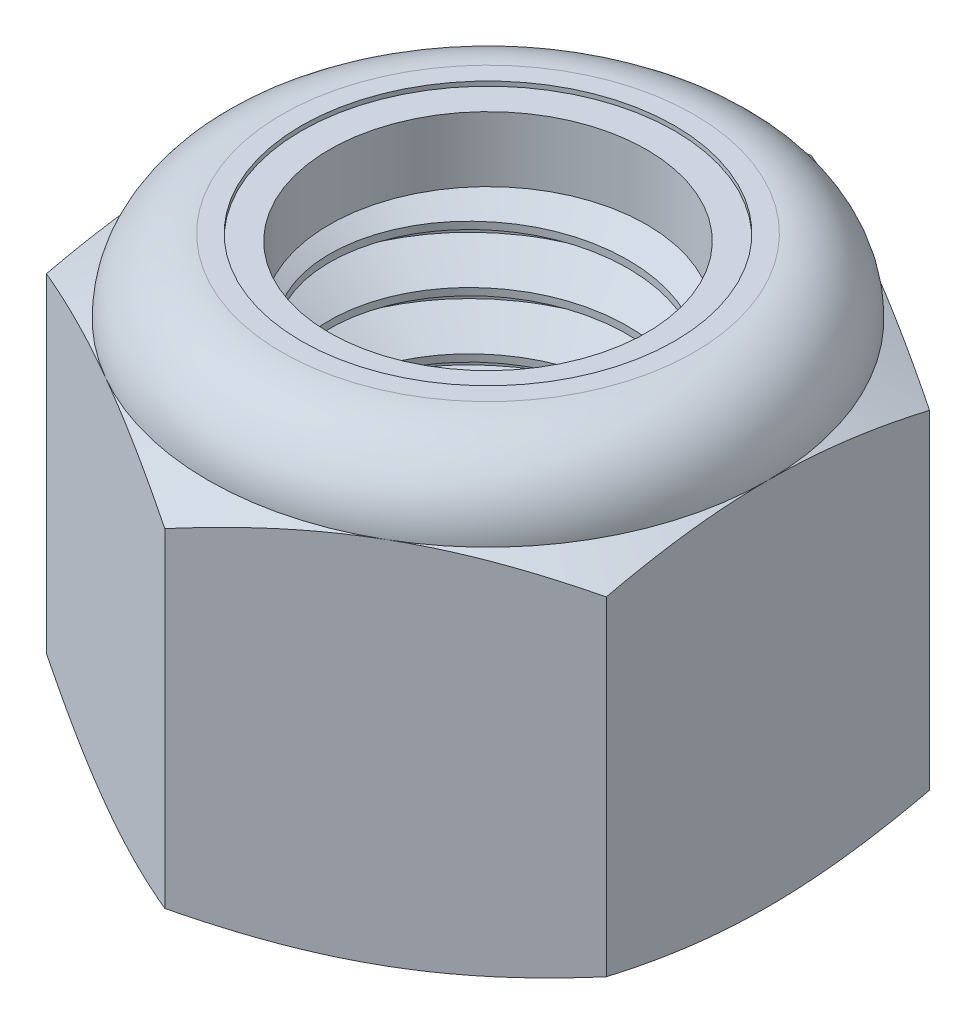
SolidWorks part; units mm, degrees
note: '?' marks a value the reader was unsure of.
ref_plane "Front" through (0, 0, 0) normal (0, 0, 1) x (1, 0, 0)
ref_plane "Top" through (0, 0, 0) normal (0, 1, 0) x (1, 0, 0)
ref_plane "Right" through (0, 0, 0) normal (1, 0, 0) x (0, 0, -1)
sketch "Sketch8" plane through (0, 0, 0) normal (1, 0, 0) x (0, 0, -1)
  line L0 (0, 0) -> (0, 15.0812) construction
  line L1 (9.525, 0) -> (-9.525, 0) construction
  line L2 (-6.35, 15.0812) -> (6.35, 15.0812) construction
  line L3 (6.35, 15.0812) -> (6.35, 13.1274) construction
sketch "Sketch1" plane through (0, 0, 0) normal (0, 1, 0) x (1, 0, 0)
  line L1 (0, 10.9985) -> (-9.525, 5.4993)
  line L2 (-9.525, 5.4993) -> (-9.525, -5.4993)
  line L3 (-9.525, -5.4993) -> (0, -10.9985)
  line L4 (0, -10.9985) -> (9.525, -5.4993)
  line L5 (9.525, -5.4993) -> (9.525, 5.4993)
  line L6 (9.525, 5.4993) -> (0, 10.9985)
  circle A0 centre (0, 0) radius 9.525 construction
  circle A1 centre (0, 0) radius 6.35
extrude "Extrude1" add sketch "Sketch1" along normal up to vertex (15.0813 mm away) up to point (0, 15.0812, 0)
sketch "Sketch5" plane through (0, 0, 0) normal (1, 0, 0) x (0, 0, -1)
  line L0 (0, 0) -> (9.525, 0)
  line L1 (9.525, 0) -> (10.9985, 0.6871)
  line L2 (10.9985, 0.6871) -> (10.9985, 11.8806)
  line L3 (10.9985, 11.8806) -> (9.525, 12.5677)
  line L4 (7.0115, 15.0812) -> (7.0115, 16.3512)
  line L5 (7.0115, 16.3512) -> (12.2685, 16.3512)
  line L6 (12.2685, 16.3512) -> (12.2685, -1.27)
  line L7 (12.2685, -1.27) -> (0, -1.27)
  line L8 (0, -1.27) -> (0, 0)
  line L9 (9.525, 12.5677) -> (9.525, 0) construction
  line L12 (10.9985, 15.0812) -> (10.9985, 0) construction
  line L13 (10.9985, 7.5406) -> (12.2685, 7.5406) construction
  line L15 (0, 0) -> (0, 16.3512) construction
  line L18 (9.525, 0) -> (-9.525, 0) construction
  line L19 (5.4993, 15.0812) -> (10.9985, 15.0812) construction
  line L20 (0, 16.3512) -> (7.0115, 16.3512) construction
  line L21 (5.4993, 0) -> (10.9985, 0) construction
  arc A0 (9.525, 12.5677) -> (7.0115, 15.0812) centre (7.0115, 12.5677) ccw
  dimension "D1" = 25
  dimension "D2" = 1.27
  dimension "D4" = 2.5135
revolve "Cut-Revolve3" cut sketch "Sketch5" angle 360 about L15
sketch "Sketch4" plane through (0, 0, 0) normal (1, 0, 0) x (0, 0, -1)
  line L0 (0, 12.5677) -> (6.985, 12.5677)
  line L1 (6.985, 12.5677) -> (0, 9.3105)
  line L3 (0, 3.2572) -> (6.985, 0)
  line L4 (6.985, 0) -> (0, 0)
  line L5 (0, 0) -> (0, 12.5677) construction
  line L10 (0, 0) -> (0, 15.0812) construction
  line L11 (0, 3.2572) -> (0, 0)
  line L12 (0, 12.5677) -> (0, 9.3105)
  line L13 (8.2489, 12.5677) -> (0, 12.5677) construction
  dimension "D1" = 25
  dimension "D2" = 13.97
sketch "Sketch6" plane through (0, 0, 0) normal (1, 0, 0) x (0, 0, -1)
  line L0 (0, 12.5677) -> (9.3726, 12.5677)
  line L1 (7.0115, 14.9288) -> (3.5057, 14.9288)
  line L2 (0, 16.3512) -> (0, 12.5677)
  line L3 (3.5057, 16.3512) -> (0, 16.3512)
  line L4 (0, 16.3512) -> (7.0115, 16.3512) construction
  line L5 (0, 0) -> (0, 16.3512) construction
  line L6 (0, 16.3512) -> (0, 0) construction
  line L7 (3.5057, 14.9288) -> (3.5057, 16.3512)
  line L8 (7.0115, 15.0812) -> (7.0115, 14.9288) construction
  line L9 (3.5057, 14.9288) -> (0, 14.9288) construction
  line L10 (0, 14.9288) -> (0, 9.3105) construction
  arc A0 (9.3726, 12.5677) -> (7.0115, 14.9288) centre (7.0115, 12.5677) ccw
  arc A1 (9.525, 12.5677) -> (7.0115, 15.0812) centre (7.0115, 12.5677) ccw construction
  dimension "D1" = 0.1524
revolve "Cut-Revolve4" cut sketch "Sketch6" angle 360 about L6
revolve "Cut-Revolve2" cut sketch "Sketch4" angle 360 about L5
sketch "Sketch7" plane through (0, 0, 0) normal (1, 0, 0) x (0, 0, -1)
  line L0 (5.3975, 12.6439) -> (9.2951, 12.6439)
  line L1 (7.0115, 14.8526) -> (5.3975, 14.8526)
  line L2 (5.3975, 14.8526) -> (5.3975, 12.6439)
  line L3 (5.3975, 12.6439) -> (0, 12.6439) construction
  line L4 (0, 12.6439) -> (0, 14.8526) construction
  line L5 (0, 14.8526) -> (5.3975, 14.8526) construction
  line L6 (5.3975, 12.6439) -> (5.3975, 12.5677) construction
  line L7 (0, 12.5677) -> (9.3726, 12.5677) construction
  line L8 (7.0115, 14.8526) -> (7.0115, 14.9288) construction
  arc A0 (9.2951, 12.6439) -> (7.0115, 14.8526) centre (7.0115, 12.5677) ccw
  arc A2 (9.3726, 12.5677) -> (7.0115, 14.9288) centre (7.0115, 12.5677) ccw construction
  dimension "D1" = 0.0762
  dimension "D2" = 10.795
revolve "Revolve2" add sketch "Sketch7" angle 360 about L4
sketch "Sketch2" plane through (0, 0, 0) normal (1, 0, 0) x (0, 0, -1)
  line L0 (-6.35, 0) -> (-6.35, 12.5677) construction
  line L1 (0, 0) -> (6.35, 0)
  line L2 (0, 0) -> (0, 12.5677)
  line L3 (0, 12.5677) -> (6.35, 12.5677)
  line L4 (6.35, 0) -> (6.35, 12.5677)
  line L6 (8.2489, 12.5677) -> (9.525, 12.5677) construction
  line L7 (0, -6.35) -> (0, 0) construction
revolve "Revolve1" add sketch "Sketch2" angle 360 about L7
sketch "Sketch9" plane through (0, 0, 0) normal (1, 0, 0) x (0, 0, -1)
  line L0 (6.5615, 14.3994) -> (6.5615, 12.4456) construction
  line L1 (6.5615, 12.4456) -> (4.8694, 13.4225) construction
  line L2 (4.8694, 13.4225) -> (6.5615, 14.3994) construction
  line L3 (5.0809, 13.5446) -> (5.0809, 13.3004) construction
  line L4 (6.35, 14.2773) -> (6.35, 12.5677) construction
  line L5 (4.8694, 13.4225) -> (5.0809, 13.4225) construction
  line L6 (6.35, 13.4225) -> (6.5615, 13.4225) construction
  line L7 (6.4558, 13.4225) -> (6.4558, 14.3384) construction
  line L8 (6.5615, 12.4456) -> (6.4558, 14.3384)
  line L9 (6.4558, 14.3384) -> (5.0809, 13.5446)
  line L10 (5.0809, 13.5446) -> (5.0809, 13.3004)
  line L11 (5.0809, 13.3004) -> (6.5615, 12.4456)
  dimension "D1" = 1.9538
  dimension "D2" = 0.2442
sketch "Sketch10" plane through (0, 12.5677, 0) normal (0, 1, 0) x (1, 0, 0)
  circle A1 centre (0, 0) radius 6.35
  circle A2 centre (0, 0) radius 6.35
  dimension "D1" = 0
curve "Helix/Spiral1" pitch 1.9538 height 17.0351 turns 8.7187
sweep "Cut-Sweep1" cut profiles "Sketch9" path "Helix/Spiral1" align with end faces yes
sketch "Sketch11" plane through (0, 0, 0) normal (1, 0, 0) x (0, 0, -1)
  line L0 (0, 0) -> (0, 15.0812) construction
  line L1 (9.525, 0) -> (-9.525, 0) construction
  line L4 (0, 15.0812) -> (0, 0) construction
  line L5 (0, 7.5406) -> (6.35, 7.5406) construction
  line L6 (0, 0) -> (6.985, 0)
  line L7 (0, 3.2572) -> (0, 0)
  line L8 (6.985, 0) -> (0, 3.2572)
  dimension "D1" = 13.97
  dimension "D2" = 25
revolve "Revolve3" add sketch "Sketch11" angle 360 about L4
sketch "Sketch12" plane through (0, 0, 0) normal (1, 0, 0) x (0, 0, -1)
  line L0 (6.985, 12.5677) -> (0, 12.5677)
  line L1 (0, 12.5677) -> (0, 0)
  line L2 (0, 0) -> (6.985, 0)
  line L3 (9.525, 0) -> (-9.525, 0) construction
  line L4 (6.985, 0) -> (6.985, 12.5677)
  line L5 (-6.985, 0) -> (6.985, 0) construction
revolve "Revolve4" add sketch "Sketch12" angle 360 about L0
combine bodies "Combine1" operation type subtract main body 136 bodies to subtract 133
ref_plane "Contact Plane 1" through (0, 0, 0) normal (0, -1, 0) x (1, 0, 0)
ref_axis "Center Axis 1" through (0, -2.1015, 0) along (0, 1, 0)?
equation "\"D4@Sketch5\"=\"Height@Sketch8\"/6"
equation "\"D1@Sketch9\"=\"Thread Pitch@Sketch8\""
equation "\"D2@Sketch9\"=\"Thread Pitch@Sketch8\"/8"
equation "\"D4@Helix/Spiral1\"=\"Thread Pitch@Sketch8\""
equation "\"D3@Helix/Spiral1\"=\"Thread Pitch@Sketch8\"+\"Height@Sketch8\""
equation "\"D2@Sketch4\"=\"Thread Dia@Sketch8\"*1.1"
equation "\"D1@Sketch11\"=\"Thread Dia@Sketch8\"*1.1"
equation "\"D2@Sketch7\"=\"Thread Dia@Sketch8\"*.85"
